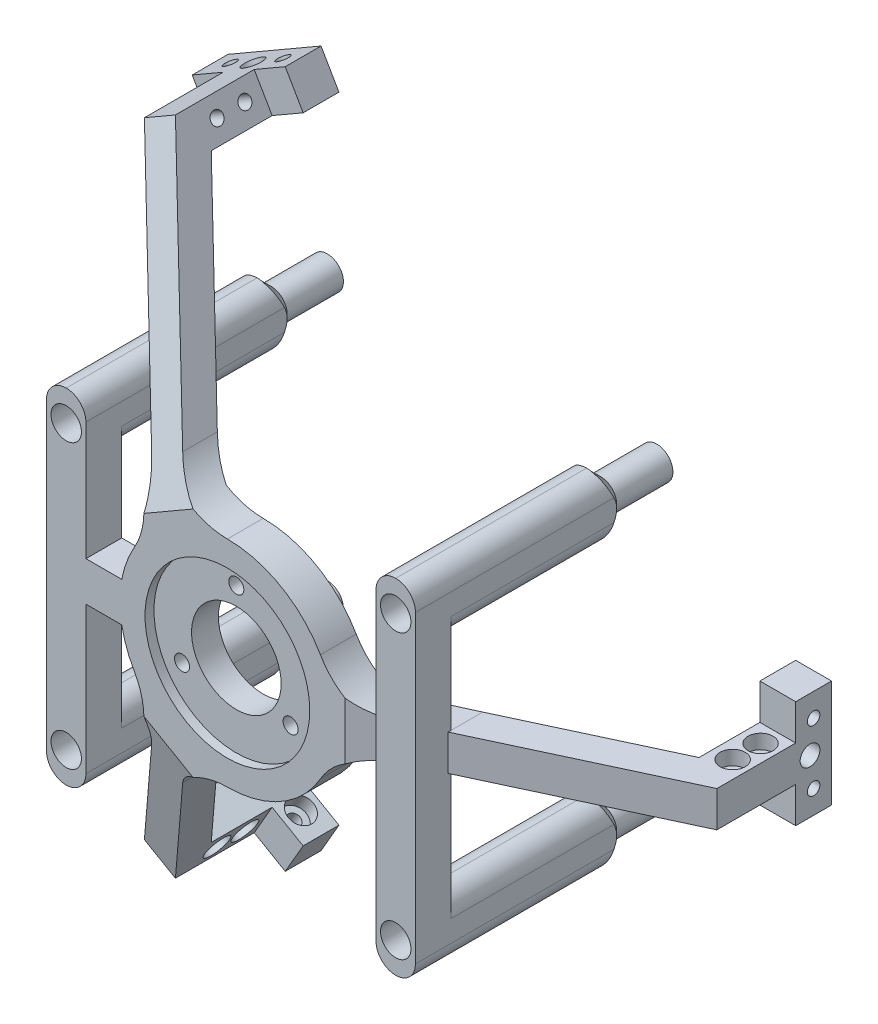
SolidWorks part; units mm, degrees
ref_plane "Plan de face" through (0, 0, 0) normal (0, 0, 1) x (1, 0, 0)
ref_plane "Plan de dessus" through (0, 0, 0) normal (0, 1, 0) x (1, 0, 0)
ref_plane "Plan de droite" through (0, 0, 0) normal (1, 0, 0) x (0, 0, -1)
sketch "Esquisse1" plane through (0, 0, 0) normal (0, 0, 1) x (1, 0, 0)
  line L0 (0, 0) -> (93.67, 0) construction
  line L1 (93.67, 15) -> (103.67, 15)
  line L2 (93.67, 15) -> (93.67, -15)
  line L3 (93.67, -15) -> (103.67, -15)
  line L4 (103.67, 15) -> (103.67, -15)
  line L5 (-33.8446, -88.6206) -> (-59.8254, -73.6206)
  line L6 (-33.8446, -88.6206) -> (-38.8446, -97.2809)
  line L7 (-38.8446, -97.2809) -> (-64.8254, -82.2809)
  line L8 (-59.8254, -73.6206) -> (-64.8254, -82.2809)
  line L9 (-59.8254, 73.6206) -> (-33.8446, 88.6206)
  line L10 (-59.8254, 73.6206) -> (-64.8254, 82.2809)
  line L11 (-64.8254, 82.2809) -> (-38.8446, 97.2809)
  line L12 (-33.8446, 88.6206) -> (-38.8446, 97.2809)
  point P17 (0, 0)
  dimension "D1" = 30
  dimension "D2" = 10
  dimension "D3" = 93.67
  dimension "D4" = 3
extrude "Boss.-Extru.1" add sketch "Esquisse1" along normal blind 10
sketch "Esquisse2" plane through (0, 0, 10) normal (0, 0, 1) x (1, 0, 0)
  line L0 (-57.0272, 86.7831) -> (-46.3532, 92.9458)
  line L1 (-38.8446, 97.2809) -> (-64.8254, 82.2809) construction
  line L2 (93.67, 15) -> (93.67, -15) construction
  line L3 (93.67, 5) -> (103.67, 5)
  line L4 (93.67, 5) -> (93.67, -5)
  line L5 (93.67, -5) -> (103.67, -5)
  line L6 (103.67, 5) -> (103.67, -5)
  line L7 (103.67, -15) -> (103.67, 15) construction
  line L8 (-42.5049, -83.6206) -> (-51.1651, -78.6206)
  line L9 (-42.5049, -83.6206) -> (-47.5049, -92.2809)
  line L10 (-47.5049, -92.2809) -> (-56.1651, -87.2809)
  line L11 (-51.1651, -78.6206) -> (-56.1651, -87.2809)
  line L12 (-51.1651, 78.6206) -> (-42.5049, 83.6206)
  line L13 (-51.1651, 78.6206) -> (-56.1651, 87.2809)
  line L14 (-56.1651, 87.2809) -> (-47.5049, 92.2809)
  line L15 (-42.5049, 83.6206) -> (-47.5049, 92.2809)
  point P12 (93.67, 0)
  point P13 (93.67, 0)
  point P24 (0, 0)
  line M6 (-59.8254, 73.6206) -> (-33.8446, 88.6206)
  dimension "D1" = 3
extrude "Boss.-Extru.2" add sketch "Esquisse2" along normal blind 45 contours L15 L0 L13 M6 | L6 L3 L4 L5 | L8 L11 L10 L9 region at (-49.335, 85.4507, 10) region at (98.67, 0, 10) region at (-49.335, -85.4507, 10)
sketch "Esquisse3" plane through (0, 0, 55) normal (0, 0, 1) x (1, 0, 0)
  line L0 (103.67, 5) -> (103.67, -5) construction
  line L1 (-47.5049, -92.2809) -> (-56.1651, -87.2809) construction
  line L2 (-47.5049, 92.2809) -> (-56.1651, 87.2809) construction
  line L3 (103.67, 5) -> (103.67, -5)
  line L4 (-47.5049, -92.2809) -> (-56.1651, -87.2809)
  line L5 (-47.5049, 92.2809) -> (-56.1651, 87.2809)
  line L6 (-56.1651, -87.2809) -> (-19.1203, -23.1174)
  line L7 (-47.5049, -92.2809) -> (-10.4601, -28.1174)
  line L8 (103.67, -5) -> (29.5804, -5)
  line L9 (103.67, 5) -> (29.5804, 5)
  line L10 (-56.1651, 87.2809) -> (-19.1203, 23.1174)
  line L11 (-47.5049, 92.2809) -> (-10.4601, 28.1174)
  line L12 (-51.1651, -78.6206) -> (-56.1651, -87.2809) construction
  line L13 (-42.5049, -83.6206) -> (-47.5049, -92.2809) construction
  line L14 (93.67, -5) -> (103.67, -5) construction
  line L15 (93.67, 5) -> (103.67, 5) construction
  line L16 (-51.1651, 78.6206) -> (-56.1651, 87.2809) construction
  line L17 (-42.5049, 83.6206) -> (-47.5049, 92.2809) construction
  arc A0 (-19.1203, -23.1174) -> (-19.1203, 23.1174) centre (0, 0) cw
  arc A1 (-10.4601, 28.1174) -> (29.5804, 5) centre (0, 0) cw
  arc A2 (29.5804, -5) -> (-10.4601, -28.1174) centre (0, 0) cw
  dimension "D1" = 30
extrude "Boss.-Extru.3" add sketch "Esquisse3" along normal blind 10
chamfer "Chanfrein1" distance 28 angle 65 3 edges at (93.67, 0, 55) (-46.835, -81.1206, 55) (-46.835, 81.1206, 55) first distance on face at (93.67, 0, 18.75) first distance on face at (-46.835, -81.1206, 18.75) first distance on face at (-46.835, 81.1206, 18.75)
chamfer "Chanfrein2" distance 33 angle 65 3 edges at (-51.835, -89.7809, 65) (-51.835, 89.7809, 65) (103.67, 0, 65) first distance on face at (-51.835, -89.7809, 21.25) first distance on face at (-51.835, 89.7809, 21.25) first distance on face at (103.67, 0, 21.25)
fillet "Congé1" radius 20 6 edges at (29.5804, -5, 60) (-10.4601, -28.1174, 60) (-19.1203, -23.1174, 60) (-19.1203, 23.1174, 60) (29.5804, 5, 60) (-10.4601, 28.1174, 60)
sketch "Esquisse4" plane through (0, 0, 65) normal (0, 0, 1) x (1, 0, 0)
  circle A0 centre (0, 0) radius 12.5
  dimension "D1" = 25
extrude "Enlèv. mat.-Extru.1" cut sketch "Esquisse4" against normal up to next
sketch "Esquisse5" plane through (0, 0, 65) normal (0, 0, 1) x (1, 0, 0)
  circle A0 centre (0, 0) radius 23
  dimension "D1" = 46
extrude "Enlèv. mat.-Extru.2" cut sketch "Esquisse5" against normal blind 2.5
sketch "Esquisse6" plane through (0, 0, 62.5) normal (0, 0, 1) x (1, 0, 0)
  line L0 (0, 17.5) -> (0, 0) construction
  circle A0 centre (0, 17.5) radius 2.1
  circle A1 centre (15.1554, -8.75) radius 2.1
  circle A2 centre (-15.1554, -8.75) radius 2.1
  point P10 (0, 0)
  dimension "D2" = 4.2
  dimension "D1" = 17.5
  dimension "D3" = 3
extrude "Enlèv. mat.-Extru.3" cut sketch "Esquisse6" against normal up to next
sketch "Esquisse7" plane through (0, 0, 55) normal (0, 0, -1) x (-1, 0, 0)
  line L0 (0, 0) -> (39.5, 0) construction
  line L1 (-41.5, -52) -> (-52.5, -52)
  line L2 (-41.5, -52) -> (-41.5, 44)
  line L3 (-41.5, 44) -> (-52.5, 44)
  line L4 (-52.5, -52) -> (-52.5, 44)
  line L5 (50.5, -52) -> (39.5, -52)
  line L6 (39.5, -52) -> (39.5, -5.5)
  line L7 (39.5, -5.5) -> (29.4915, -5.5)
  line L8 (50.5, -52) -> (50.5, 44)
  line L9 (50.5, 44) -> (39.5, 44)
  line L10 (39.5, 44) -> (39.5, 5.5)
  line L11 (39.5, 5.5) -> (29.4915, 5.5)
  line L12 (39.5, -5.5) -> (39.5, 5.5) construction
  arc A0 (25.9808, -15) -> (25.9808, 15) centre (0, 0) ccw construction
  arc A1 (29.4915, -5.5) -> (29.4915, 5.5) centre (0, 0) ccw
  point P7 (-47, 44)
  point P21 (45, 44)
  point P22 (39.5, 0)
  dimension "D1" = 11
  dimension "D2" = 52
  dimension "D3" = 96
  dimension "D4" = 47
  dimension "D5" = 92
extrude "Boss.-Extru.4" add sketch "Esquisse7" along normal blind 43.3 and the other way up to surface (10 mm away) other way up to face at (23, 0, 65)
sketch "Esquisse8" plane through (0, 0, 11.7) normal (0, 0, -1) x (-1, 0, 0)
  line L0 (-52.5, -4) -> (50.5, -4) construction
  line L1 (-52.5, 44) -> (-52.5, -52) construction
  line L2 (50.5, -52) -> (50.5, 44) construction
  line L3 (45, 35.5) -> (-47, 35.5) construction
  line L4 (-1, -4) -> (-1, 35.5) construction
  line L5 (-52.5, -52) -> (-41.5, -52) construction
  circle A0 centre (45, 35.5) radius 4.25
  circle A1 centre (-47, 35.5) radius 4.25
  circle A2 centre (-47, -43.5) radius 4.25
  circle A3 centre (45, -43.5) radius 4.25
  dimension "D4" = 8.5
  dimension "D1" = 92
  dimension "D2" = 79
  dimension "D3" = 8.5
extrude "Enlèv. mat.-Extru.4" cut sketch "Esquisse8" against normal up to next
sketch "Esquisse18" plane through (0, 0, 11.7) normal (0, 0, -1) x (-1, 0, 0)
  circle A0 centre (-47, 35.5) radius 4.5
  circle A1 centre (-47, -43.5) radius 4.5
  circle A2 centre (45, 35.5) radius 4.5
  circle A3 centre (45, -43.5) radius 4.5
  circle A12 centre (45, 35.5) radius 2.5
  circle A13 centre (-47, 35.5) radius 2.5
  circle A14 centre (-47, -43.5) radius 2.5
  circle A15 centre (45, -43.5) radius 2.5
  dimension "D1" = 9
  dimension "D2" = 5
extrude "Boss.-Extru.6" add sketch "Esquisse18" along normal blind 17.6
chamfer "Chanfrein3" distance 3.9 angle 45 4 edges at (42.5, -43.5, 11.7) (42.5, 35.5, 11.7) (-49.5, -43.5, 11.7) (-49.5, 35.5, 11.7)
sketch "Esquisse19" plane through (0, 0, -5.9) normal (0, 0, -1) x (-1, 0, 0)
  circle A0 centre (-47, -43.5) radius 4.5 construction
  circle A1 centre (-47, 35.5) radius 4.5 construction
  circle A2 centre (45, 35.5) radius 4.5 construction
  circle A3 centre (45, -43.5) radius 4.5 construction
  circle A4 centre (-47, -43.5) radius 4.5
  circle A5 centre (-47, 35.5) radius 4.5
  circle A6 centre (45, 35.5) radius 4.5
  circle A7 centre (45, -43.5) radius 4.5
  circle A8 centre (-47, -43.5) radius 1.5
  circle A9 centre (-47, 35.5) radius 1.5
  circle A10 centre (45, 35.5) radius 1.5
  circle A11 centre (45, -43.5) radius 1.5
  dimension "D1" = 3
extrude "Boss.-Extru.7" add sketch "Esquisse19" along normal blind 2
sketch "Esquisse10" plane through (0, 0, 11.7) normal (0, 0, -1) x (-1, 0, 0)
  line L6 (50.5, -52) -> (50.5, -49.849) construction
  line L7 (50.5, -35) -> (29.4915, -35)
  line L8 (50.5, -35) -> (50.5, 27)
  line L9 (50.5, 27) -> (29.4915, 27)
  line L10 (29.4915, -35) -> (29.4915, 27)
  line L11 (45, 35.5) -> (45, 27) construction
  line L12 (45, -43.5) -> (45, -35) construction
  line L13 (-52.5, 44) -> (-52.5, 41.849) construction
  line L14 (-52.5, 27) -> (-41.5, 27)
  line L15 (-52.5, 27) -> (-52.5, -35)
  line L16 (-52.5, -35) -> (-41.5, -35)
  line L17 (-41.5, 27) -> (-41.5, -35)
  line L18 (-41.5, -52) -> (-41.5, -49.849) construction
  dimension "D1" = 8.5
extrude "Enlèv. mat.-Extru.6" cut sketch "Esquisse10" against normal up to surface (43.3 mm away) up to face at (-2.1, 17.5, 55)
sketch "Esquisse17" plane through (0, 0, 55) normal (0, 0, -1) x (-1, 0, 0)
  line L0 (-41.5, -5.0813) -> (-52.5, -5)
  line L1 (-52.5, -5) -> (-52.5, 5)
  line L2 (-52.5, 5) -> (-41.5, 5.0813)
  line L3 (-41.5, 5.0813) -> (-41.5, -5.0813)
extrude "Boss.-Extru.5" add sketch "Esquisse17" along normal up to surface (8.8021 mm away) contours L3 L0 L1 L2 up to face at (73.085, 0, 36.5989)
fillet "Congé2" radius 5.5 16 edges at (-50.5, 44, 38.35) (-39.5, 44, 38.35) (41.5, 44, 38.35) (52.5, 44, 38.35) (-50.5, -52, 38.35) (-39.5, -52, 38.35) (52.5, -52, 38.35) (41.5, -52, 38.35) (-50.5, 27, 33.35) (-39.5, 27, 33.35) (-50.5, -35, 33.35) (-39.5, -35, 33.35) (41.5, -35, 33.35) (52.5, -35, 33.35) (41.5, 27, 33.35) (52.5, 27, 33.35)
sketch "Esquisse11" plane through (4.3301, -2.5, 0) normal (0.866, -0.5, 0) x (0, 0, -1)
  line L0 (-27, -93.67) -> (-10, -93.67) construction
  line L1 (-10, -93.67) -> (-10, -103.67) construction
  circle A0 centre (-15, -98.86) radius 1.75
  circle A1 centre (-22.78, -98.86) radius 1.75
  dimension "D4" = 3.5
  dimension "D1" = 5.19
  dimension "D2" = 5
  dimension "D3" = 7.78
extrude "Enlèv. mat.-Extru.7" cut sketch "Esquisse11" against normal up to next
sketch "Esquisse12" plane through (4.3301, -2.5, 0) normal (0.866, -0.5, 0) x (0, 0, -1)
  circle A0 centre (-15, -98.86) radius 3.5
  circle A1 centre (-22.78, -98.86) radius 3.5
  dimension "D1" = 7
extrude "Enlèv. mat.-Extru.8" cut sketch "Esquisse12" against normal blind 4
sketch "Esquisse13" plane through (-46.835, -81.1206, 0) normal (0.5, 0.866, 0) x (0.866, -0.5, 0)
  line L0 (-15, -10) -> (-15, 0) construction
  line L1 (-15, -5) -> (-8.5, -5) construction
  line L2 (15, -5) -> (8.5, -5) construction
  line L3 (15, -10) -> (15, 0) construction
  circle A0 centre (-8.5, -5) radius 1.75
  circle A1 centre (8.5, -5) radius 1.75
  dimension "D2" = 3.5
  dimension "D1" = 6.5
extrude "Enlèv. mat.-Extru.9" cut sketch "Esquisse13" against normal up to next
sketch "Esquisse14" plane through (-46.835, -81.1206, 0) normal (0.5, 0.866, 0) x (0.866, -0.5, 0)
  circle A0 centre (-8.5, -5) radius 3.5
  circle A1 centre (8.5, -5) radius 3.5
  dimension "D1" = 7
extrude "Enlèv. mat.-Extru.10" cut sketch "Esquisse14" against normal blind 4
sketch "Esquisse15" plane through (-46.835, -81.1206, 0) normal (0.5, 0.866, 0) x (0.866, -0.5, 0)
  line L0 (15, 0) -> (-15, 0) construction
  line L1 (-15, -10) -> (-15, 0) construction
  circle A0 centre (0, -6) radius 2.75
  point P5 (0, 0)
  point P8 (-15, -5)
  dimension "D1" = 5.5
  dimension "D2" = 1
extrude "Enlèv. mat.-Extru.11" cut sketch "Esquisse15" against normal up to next
pattern_circular "Répétition circulaire1" count 3 over 360 about axis through (0, 0, -0.001) along (0, 0, 1) of "Enlèv. mat.-Extru.7", "Enlèv. mat.-Extru.11", "Enlèv. mat.-Extru.10", "Enlèv. mat.-Extru.9", "Enlèv. mat.-Extru.8" reverse direction yes
